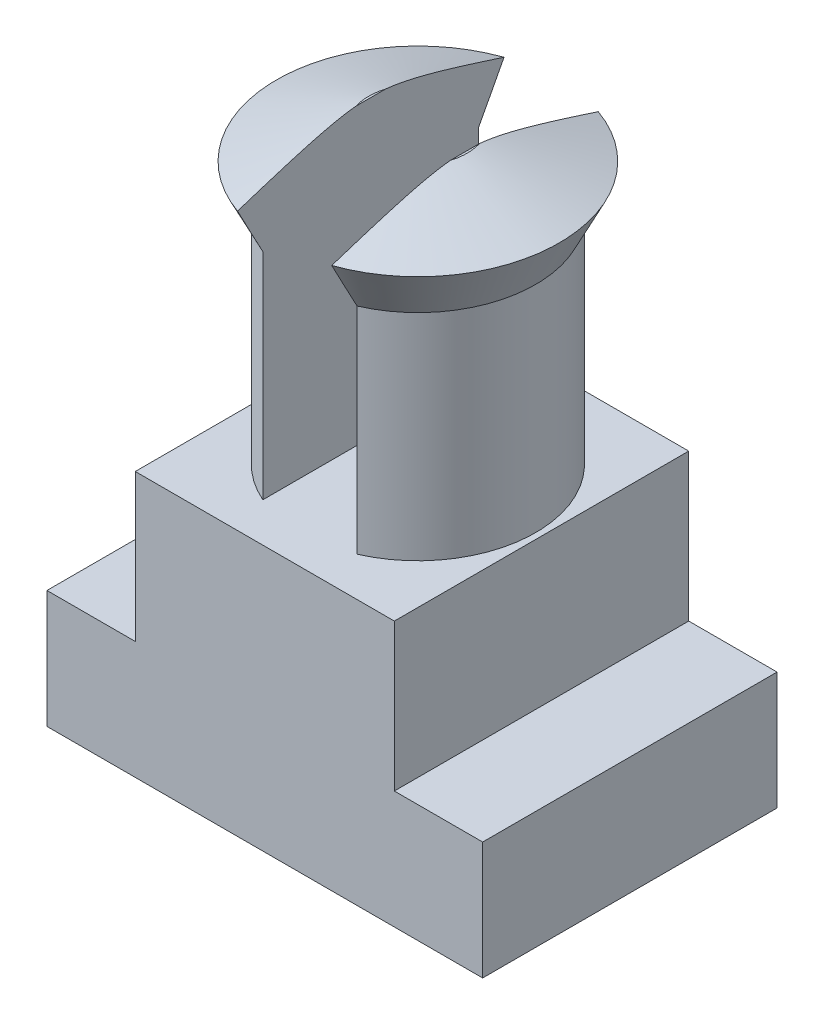
SolidWorks part; units mm, degrees
ref_plane "Front Plane" through (0, 0, 0) normal (0, 0, 1) x (1, 0, 0)
ref_plane "Top Plane" through (0, 0, 0) normal (0, 1, 0) x (1, 0, 0)
ref_plane "Right Plane" through (0, 0, 0) normal (1, 0, 0) x (0, 0, -1)
sketch "Sketch1" plane through (0, 0, 0) normal (0, 0, 1) x (1, 0, 0)
  line L0 (0, 0) -> (9.398, 0)
  line L1 (0, 0) -> (0, 2.54)
  line L2 (0, 2.54) -> (1.905, 2.54)
  line L3 (1.905, 2.54) -> (1.905, 5.715)
  line L4 (1.905, 5.715) -> (7.493, 5.715)
  line L5 (7.493, 5.715) -> (7.493, 2.54)
  line L6 (7.493, 2.54) -> (9.398, 2.54)
  line L7 (9.398, 2.54) -> (9.398, 0)
  dimension "D1" = 9.398
  dimension "D2" = 2.54
  dimension "D3" = 1.905
  dimension "D4" = 5.588
  dimension "D5" = 2.54
  dimension "D6" = 3.175
extrude "Boss-Extrude1" add sketch "Sketch1" along normal mid plane 6.35
sketch "Sketch2" plane through (0, 5.715, 0) normal (0, 1, 0) x (1, 0, 0)
  circle A0 centre (4.826, 0) radius 2.54
  dimension "D1" = 5.08
sketch "Sketch3" plane through (0, 0, 0) normal (0, 0, 1) x (1, 0, 0)
  line L0 (4.826, 5.715) -> (4.826, 15.7401) construction
  line L2 (3.7622, 12.065) -> (4.3265, 12.065)
  line L3 (4.3265, 12.065) -> (4.3265, 5.715)
  line L4 (7.366, 5.715) -> (2.286, 5.715) construction
  line L5 (4.3265, 5.715) -> (2.286, 5.715)
  line L6 (7.493, 5.715) -> (1.905, 5.715) construction
  line L7 (2.286, 5.715) -> (2.286, 10.3505)
  line L8 (2.286, 10.3505) -> (1.778, 11.3805)
  line L9 (1.778, 11.3805) -> (3.7622, 12.065)
  dimension "D1" = 6.35
  dimension "D2" = 4.6355
  dimension "D3" = 3.048
  dimension "D4" = 2.54
revolve "Revolve1" add sketch "Sketch3" angle 360 about L0
sketch "Sketch4" plane through (0, 0, 0) normal (0, 0, 1) x (1, 0, 0)
  line L0 (5.3255, 12.065) -> (4.3265, 12.065) construction
  line L1 (3.81, 18.415) -> (5.842, 18.415)
  line L2 (3.81, 18.415) -> (3.81, 5.715)
  line L3 (3.81, 5.715) -> (5.842, 5.715)
  line L4 (5.842, 18.415) -> (5.842, 5.715)
  line L5 (3.81, 18.415) -> (5.842, 5.715) construction
  line L6 (3.81, 5.715) -> (5.842, 18.415) construction
  line L7 (7.366, 5.715) -> (2.286, 5.715) construction
  point P0 (4.826, 12.065)
  dimension "D1" = 2.032
extrude "Cut-Extrude1" cut sketch "Sketch4" against normal through all both and the other way through all
